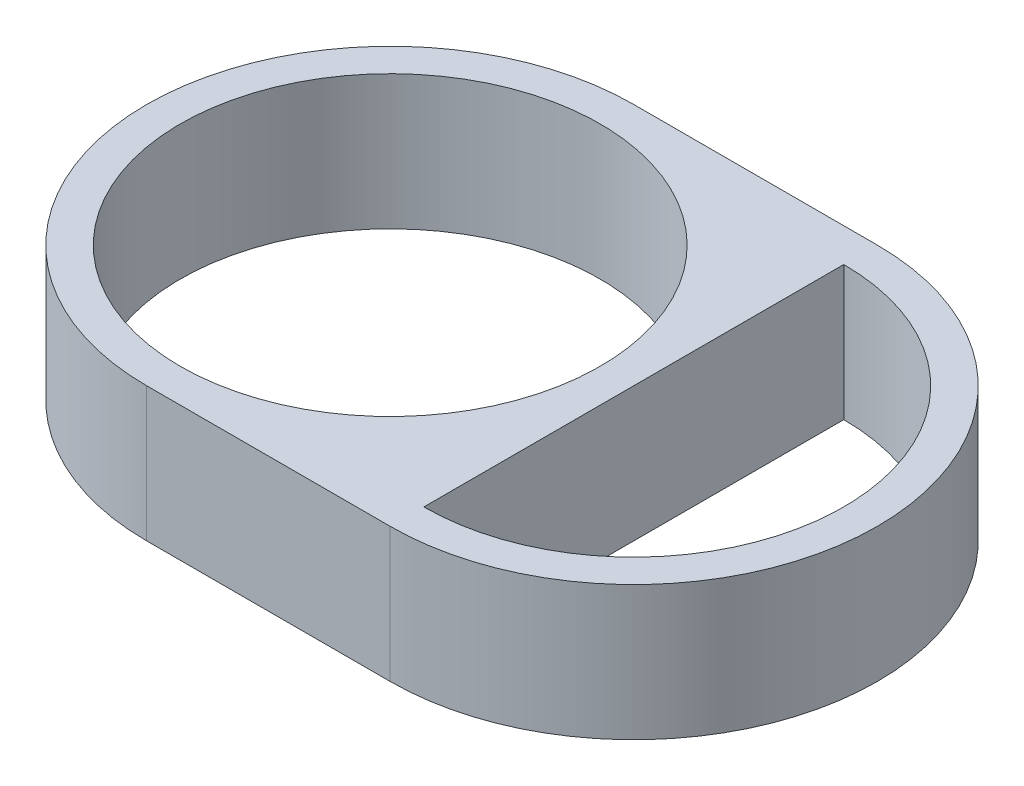
SolidWorks part; units mm, degrees
material "1060 合金"
ref_plane "前视基准面" through (0, 0, 0) normal (0, 0, 1) x (1, 0, 0)
ref_plane "上视基准面" through (0, 0, 0) normal (0, 1, 0) x (1, 0, 0)
ref_plane "右视基准面" through (0, 0, 0) normal (1, 0, 0) x (0, 0, -1)
sketch "草图1" plane through (0, 0, 0) normal (0, 1, 0) x (1, 0, 0)
  line L0 (0, -14.5) -> (14.5, -14.5)
  line L1 (14.5, -14.5) -> (14.5, 14.5)
  line L3 (14.5, 14.5) -> (0, 14.5)
  circle A0 centre (0, 0) radius 12.5
  arc A1 (0, 14.5) -> (0, -14.5) centre (0, 0) ccw
  arc A2 (14.5, 14.5) -> (14.5, -14.5) centre (14.5, 0) cw
  arc A3 (14.5, 12.5) -> (14.5, -12.5) centre (14.5, 0) cw
extrude "凸台-拉伸1" add sketch "草图1" along normal blind 8 contours L3 A1 L0 A0 region at (-14.0899, 0, 0)
extrude "凸台-拉伸2" add sketch "草图1<3>" along normal blind 8 contours A2 region at (14.8242, 0, 13.5)
sketch "草图1<3>" plane through (0, 0, 0) normal (0, 1, 0) x (1, 0, 0) same geometry as "草图1"
ref_plane "基准面1" through (0, 8, 0) normal (0, 1, 0) x (1, 0, 0)
